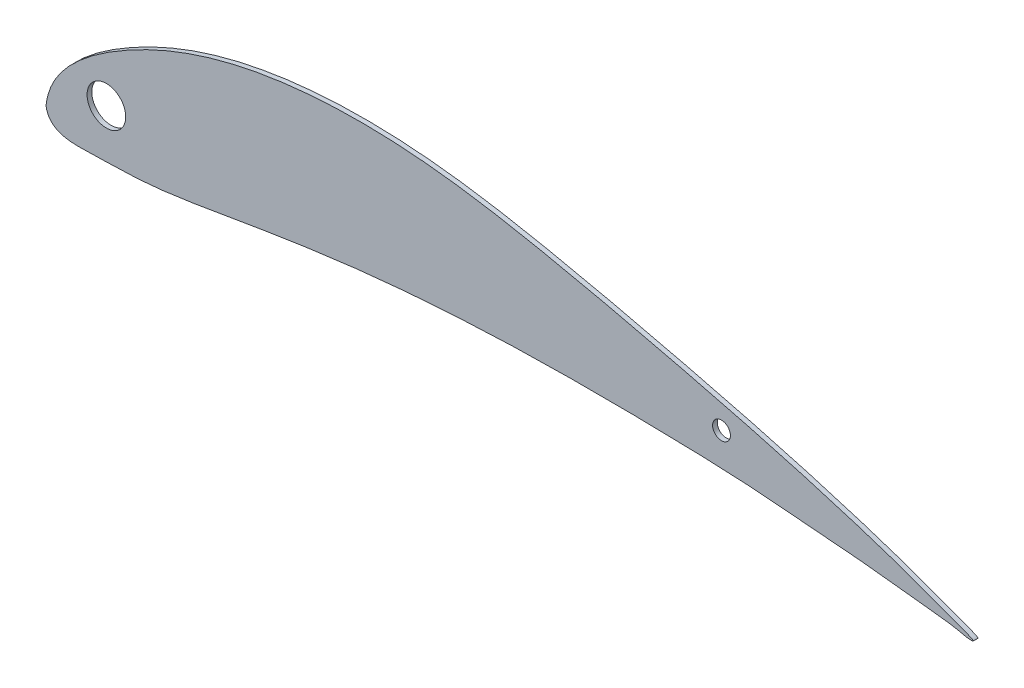
SolidWorks part; units mm, degrees
material "Balsa"
ref_plane "Front Plane" through (0, 0, 0) normal (0, 0, 1) x (1, 0, 0)
ref_plane "Top Plane" through (0, 0, 0) normal (0, 1, 0) x (1, 0, 0)
ref_plane "Right Plane" through (0, 0, 0) normal (1, 0, 0) x (0, 0, -1)
sketch "Sketch1" plane through (0, 0, 0) normal (0, 0, 1) x (1, 0, 0)
  spline S0 degree 3 poles (0.0006, 0.0001) (0.8106, 7.3592) (8.6491, 17.8566) (26.2867, 29.9752) (52.1111, 42.0692) (89.5976, 49.2908) (131.4008, 47.8848) (173.2567, 40.0411) (217.9611, 29.613) (256.9521, 19.5289) (290.3598, 8.711) (301.2732, 4.3828) (314.8169, -0.5162) (309.8463, 0.0001) knots 0 0 0 0 0.060864 0.113688 0.188609 0.312909 0.448482 0.557612 0.691544 0.852438 0.929756 0.976058 1 1 1 1
  spline S1 degree 3 poles (309.8463, 0.0001) (303.9568, 1.471) (293.9895, 2.094) (276.264, 4.5144) (260.8463, 5.4274) (235.8588, 7.8703) (205.1014, 8.8381) (157.7186, 9.0307) (110.4973, 6.1815) (66.5062, -0.5867) (36.4547, -6.0985) (15.3166, -6.1891) (1.2307, -6.9241) (0.0006, 0.0001) knots 0 0 0 0 0.057787 0.095275 0.171021 0.205339 0.335319 0.464904 0.658702 0.785512 0.893517 0.943092 1 1 1 1
extrude "Boss-Extrude1" add sketch "Sketch1" along normal blind 1.5875
sketch "Sketch2" plane through (0, 0, 1.5875) normal (0, 0, 1) x (1, 0, 0)
  circle A0 centre (20.32, 10.16) radius 6.5
  circle A1 centre (227.2963, 19.0501) radius 3
  dimension "D2" = 13
  dimension "D3" = 6
  dimension "D6" = 20.32
  dimension "D1" = 82.55
  dimension "D4" = 19.05
  dimension "D5" = 10.16
extrude "Cut-Extrude1" cut sketch "Sketch2" against normal through all
